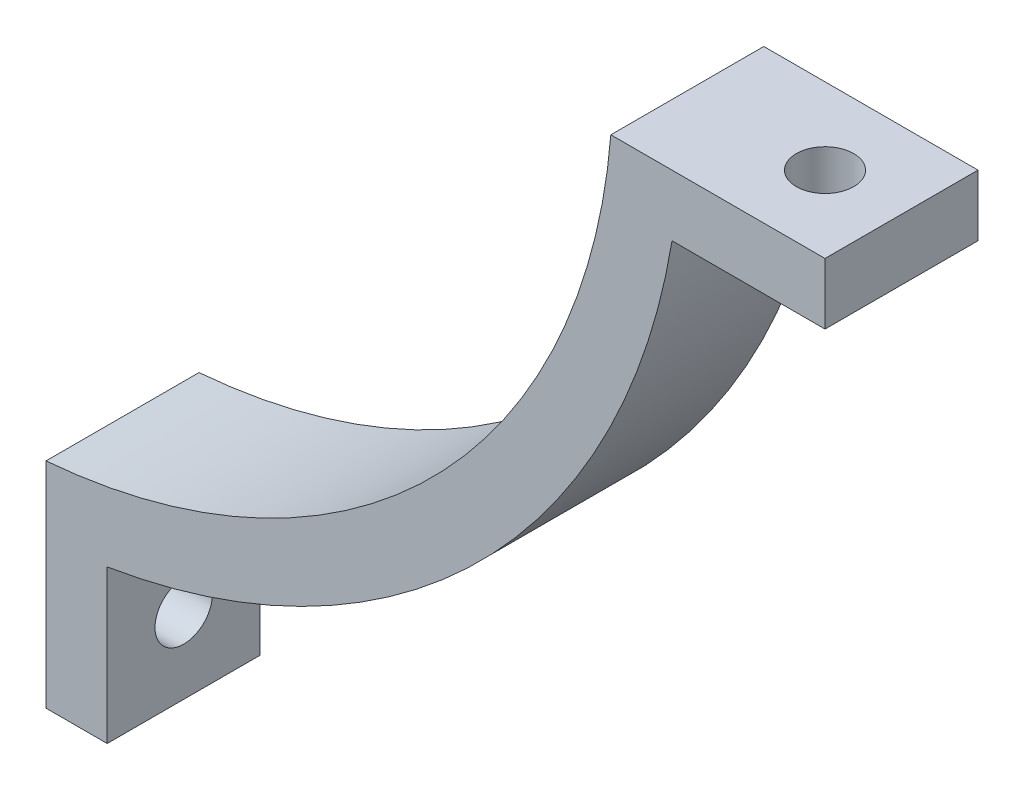
SolidWorks part; units mm, degrees
ref_plane "Front Plane" through (0, 0, 0) normal (0, 0, 1) x (1, 0, 0)
ref_plane "Top Plane" through (0, 0, 0) normal (0, 1, 0) x (1, 0, 0)
ref_plane "Right Plane" through (0, 0, 0) normal (1, 0, 0) x (0, 0, -1)
sketch "Sketch1" plane through (0, 0, 0) normal (0, 0, 1) x (1, 0, 0)
  line L0 (-230.4035, 0) -> (230.4035, 0) construction
  line L1 (0, 230.4035) -> (0, -230.4035) construction
  line L2 (230.4035, -3.937) -> (230.4035, 3.937) construction
  line L3 (230.4035, 3.937) -> (50.8255, 3.937) construction
  line L4 (-230.4035, -3.937) -> (-230.4035, 3.937) construction
  line L5 (230.4035, -3.937) -> (50.8255, -3.937) construction
  line L6 (-230.4035, 3.937) -> (-50.8255, 3.937) construction
  line L7 (-230.4035, -3.937) -> (-50.8255, -3.937) construction
  line L8 (-3.937, -230.4035) -> (3.937, -230.4035) construction
  line L9 (3.937, -230.4035) -> (3.937, -50.8255) construction
  line L10 (-3.937, -230.4035) -> (-3.937, -50.8255) construction
  line L11 (-3.937, 230.4035) -> (-3.937, 50.8255) construction
  line L12 (-3.937, 230.4035) -> (3.937, 230.4035) construction
  line L13 (3.937, 230.4035) -> (3.937, 50.8255) construction
  line L14 (51.0795, -4.191) -> (68.8595, -4.191)
  line L15 (68.8595, -4.191) -> (68.8595, -9.271)
  line L16 (4.191, -51.0795) -> (4.191, -68.8595)
  line L17 (4.191, -68.8595) -> (9.271, -68.8595)
  line L18 (9.271, -68.8595) -> (9.271, -56.1595)
  line L19 (68.8595, -9.271) -> (56.1595, -9.271)
  circle A0 centre (0, 0) radius 50.9778 construction
  arc A1 (51.0795, -4.191) -> (4.191, -51.0795) centre (0, 0) cw
  arc A2 (56.1595, -9.271) -> (9.271, -56.1595) centre (0, 0) cw
  point P6 (0, 0)
  point P9 (0, 0)
  point P10 (0, 0)
  point P18 (-230.4035, 0)
  point P20 (0, -230.4035)
  dimension "D3" = 101.9556
  dimension "D4" = 7.874
  dimension "D5" = 179.578
  dimension "D1" = 0.254
  dimension "D2" = 0.254
  dimension "D6" = 0.254
  dimension "D7" = 7.874
  dimension "D8" = 179.578
  dimension "D9" = 179.578
extrude "Boss-Extrude3" add sketch "Sketch1" along normal blind 12.7
sketch "Sketch2" plane through (9.271, 0, 0) normal (1, 0, 0) x (0, 0, -1)
  line L0 (-12.7, -68.8595) -> (-12.7, -56.1595) construction
  line L1 (-12.7, -68.8595) -> (0, -68.8595) construction
  circle A0 centre (-6.35, -62.5095) radius 2.3812
  dimension "D1" = 4.7625
  dimension "D2" = 6.35
  dimension "D3" = 6.35
extrude "Cut-Extrude1" cut sketch "Sketch2" against normal blind 5.08
sketch "Sketch3" plane through (0, -9.271, 0) normal (0, -1, 0) x (1, 0, 0)
  line L0 (68.8595, 12.7) -> (68.8595, 0) construction
  line L1 (56.1595, 12.7) -> (68.8595, 12.7) construction
  circle A0 centre (62.5095, 6.35) radius 2.3813
  point P6 (0, 0)
  dimension "D1" = 6.35
  dimension "D3" = 4.7625
  dimension "D2" = 6.35
extrude "Cut-Extrude2" cut sketch "Sketch3" against normal blind 5.08
equation "\"Fin Thickness\"= 0.31in"
equation "\"D4@Sketch1\"=\"Fin Thickness\""
equation "\"Fin Length\"= 7.07in"
equation "\"D5@Sketch1\"=\"Fin Length\""
equation "\"Outer Diameter\"= 4.014in"
equation "\"D3@Sketch1\"=\"Outer Diameter\""
equation "\"D7@Sketch1\"=\"Fin Thickness\""
equation "\"D8@Sketch1\"=\"Fin Length\""
equation "\"D9@Sketch1\"=\"Fin Length\""
